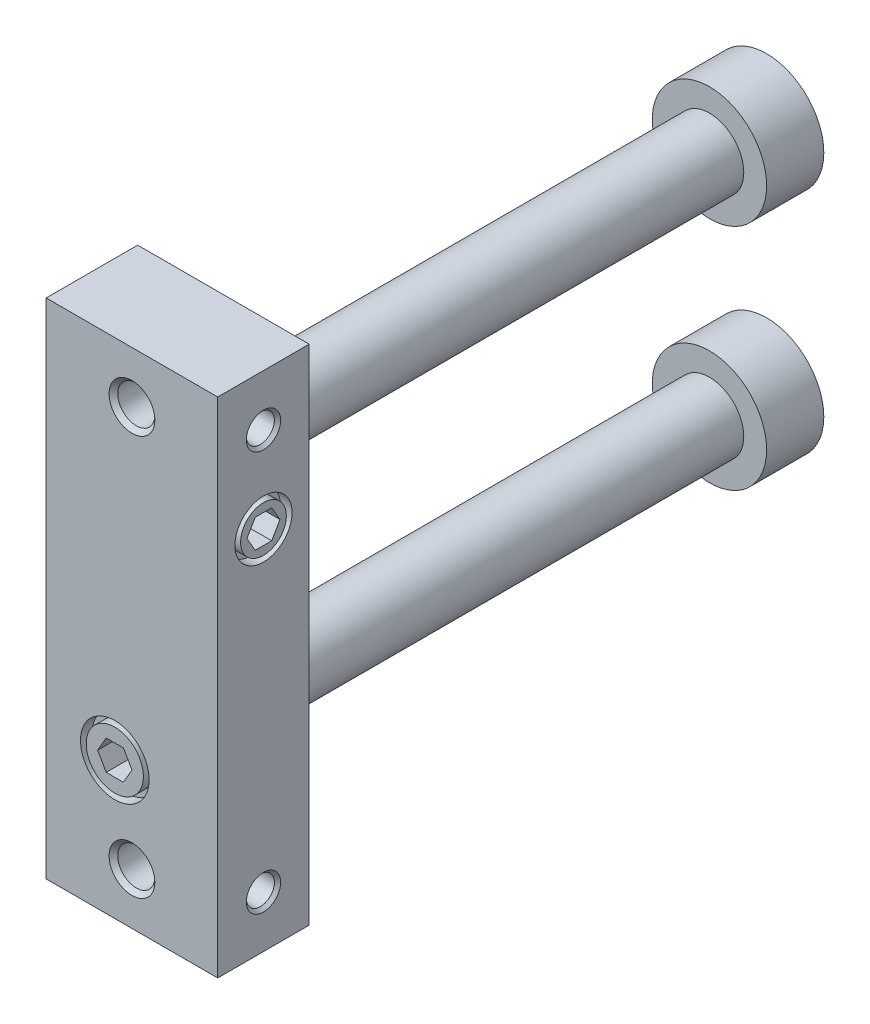
SolidWorks part; units mm, degrees
ref_plane "前视基准面" through (0, 0, 0) normal (0, 0, 1) x (1, 0, 0)
ref_plane "上视基准面" through (0, 0, 0) normal (0, 1, 0) x (1, 0, 0)
ref_plane "右视基准面" through (0, 0, 0) normal (1, 0, 0) x (0, 0, -1)
ref_plane "基准面1" through (0, 0, 9) normal (0, 0, 1) x (1, 0, 0)
sketch "草图1" plane through (0, 0, 9) normal (0, 0, 1) x (1, 0, 0)
  line L0 (-6, 22) -> (-6, -22)
  line L1 (-6, -22) -> (9, -22)
  line L2 (9, -22) -> (9, 22)
  line L3 (9, 22) -> (-6, 22)
extrude "凸台-拉伸1" add sketch "草图1" along normal blind 8
sketch "草图2" plane through (0, 0, 0) normal (1, 0, 0) x (0, 0, -1)
  line L0 (-14, 10) -> (-14, 13)
  line L1 (-14, 13) -> (35, 13)
  line L2 (35, 13) -> (35, 15)
  line L3 (35, 15) -> (40, 15)
  line L4 (40, 15) -> (40, 10)
  line L5 (40, 10) -> (-14, 10)
  line L6 (40, 10) -> (-14, 10) construction
revolve "旋转1" add sketch "草图2" angle 360 about L6 reverse direction yes
sketch "草图3" plane through (0, 0, 0) normal (1, 0, 0) x (0, 0, -1)
  line L0 (-14, -10) -> (-14, -7)
  line L1 (-14, -7) -> (35, -7)
  line L2 (35, -7) -> (35, -5)
  line L3 (35, -5) -> (40, -5)
  line L4 (40, -5) -> (40, -10)
  line L5 (40, -10) -> (-14, -10)
  line L6 (40, -10) -> (-14, -10) construction
revolve "旋转2" add sketch "草图3" angle 360 about L6 reverse direction yes
ref_plane "基准面2" through (1.5, 0, 0) normal (1, 0, 0) x (0, 0, -1)
sketch "草图4" plane through (1.5, 0, 0) normal (1, 0, 0) x (0, 0, -1)
  line L0 (-17, 17.5) -> (-17, 19.5)
  line L1 (-17, 19.5) -> (-16.621, 19.121)
  line L2 (-16.621, 19.121) -> (-9.379, 19.121)
  line L3 (-9.379, 19.121) -> (-9, 19.5)
  line L4 (-9, 19.5) -> (-9, 17.5)
  line L5 (-9, 17.5) -> (-17, 17.5)
  line L6 (-9, 17.5) -> (-17, 17.5) construction
revolve "切除-旋转1" cut sketch "草图4" angle 360 about L6 reverse direction yes
cosmetic thread "装饰螺纹线1" parameters "D1"=8, "D2"=4
sketch "草图5" plane through (1.5, 0, 0) normal (1, 0, 0) x (0, 0, -1)
  line L0 (-17, -17.5) -> (-17, -15.5)
  line L1 (-17, -15.5) -> (-16.621, -15.879)
  line L2 (-16.621, -15.879) -> (-9.379, -15.879)
  line L3 (-9.379, -15.879) -> (-9, -15.5)
  line L4 (-9, -15.5) -> (-9, -17.5)
  line L5 (-9, -17.5) -> (-17, -17.5)
  line L6 (-9, -17.5) -> (-17, -17.5) construction
revolve "切除-旋转2" cut sketch "草图5" angle 360 about L6 reverse direction yes
cosmetic thread "装饰螺纹线2" parameters "D1"=8, "D2"=4
ref_plane "基准面3" through (0, 0, 13) normal (0, 0, 1) x (1, 0, 0)
sketch "草图6" plane through (0, 0, 13) normal (0, 0, 1) x (1, 0, 0)
  line L0 (-6, 17.5) -> (-6, 19)
  line L1 (-6, 19) -> (-5.7295, 18.7295)
  line L2 (-5.7295, 18.7295) -> (-1, 18.7295)
  line L3 (-1, 18.7295) -> (-0.2901, 17.5)
  line L4 (-0.2901, 17.5) -> (-6, 17.5)
  line L5 (-0.2901, 17.5) -> (-6, 17.5) construction
revolve "切除-旋转3" cut sketch "草图6" angle 360 about L5 reverse direction yes
cosmetic thread "装饰螺纹线3" parameters "D1"=5, "D2"=3
sketch "草图7" plane through (0, 0, 13) normal (0, 0, 1) x (1, 0, 0)
  line L0 (-0.2901, -17.5) -> (-1, -18.7295)
  line L1 (-1, -18.7295) -> (-5.7295, -18.7295)
  line L2 (-5.7295, -18.7295) -> (-6, -19)
  line L3 (-6, -19) -> (-6, -17.5)
  line L4 (-6, -17.5) -> (-0.2901, -17.5)
  line L5 (-6, -17.5) -> (-0.2901, -17.5) construction
revolve "切除-旋转4" cut sketch "草图7" angle 360 about L5 reverse direction yes
cosmetic thread "装饰螺纹线4" parameters "D1"=5, "D2"=3
sketch "草图8" plane through (0, 0, 13) normal (0, 0, 1) x (1, 0, 0)
  line L0 (3.2901, 17.5) -> (4, 18.7295)
  line L1 (4, 18.7295) -> (8.7295, 18.7295)
  line L2 (8.7295, 18.7295) -> (9, 19)
  line L3 (9, 19) -> (9, 17.5)
  line L4 (9, 17.5) -> (3.2901, 17.5)
  line L5 (9, 17.5) -> (3.2901, 17.5) construction
revolve "切除-旋转5" cut sketch "草图8" angle 360 about L5 reverse direction yes
cosmetic thread "装饰螺纹线5" parameters "D1"=5, "D2"=3
sketch "草图9" plane through (0, 0, 13) normal (0, 0, 1) x (1, 0, 0)
  line L0 (9, -17.5) -> (9, -19)
  line L1 (9, -19) -> (8.7295, -18.7295)
  line L2 (8.7295, -18.7295) -> (4, -18.7295)
  line L3 (4, -18.7295) -> (3.2901, -17.5)
  line L4 (3.2901, -17.5) -> (9, -17.5)
  line L5 (3.2901, -17.5) -> (9, -17.5) construction
revolve "切除-旋转6" cut sketch "草图9" angle 360 about L5 reverse direction yes
cosmetic thread "装饰螺纹线6" parameters "D1"=5, "D2"=3
ref_plane "基准面4" through (0, 0, 17) normal (0, 0, 1) x (1, 0, 0)
sketch "草图10" plane through (0, 0, 17) normal (0, 0, 1) x (1, 0, 0)
  circle A0 centre (0, -10) radius 3
  circle A1 centre (0, -10) radius 2.5
extrude "切除-拉伸1" cut sketch "草图10" against normal blind 1
sketch "草图11" plane through (0, 0, 17) normal (0, 0, 1) x (1, 0, 0)
  line L0 (-1.5011, -10) -> (-0.7506, -11.3)
  line L1 (-0.7506, -11.3) -> (0.7506, -11.3)
  line L2 (0.7506, -11.3) -> (1.5011, -10)
  line L3 (1.5011, -10) -> (0.7506, -8.7)
  line L4 (0.7506, -8.7) -> (-0.7506, -8.7)
  line L5 (-0.7506, -8.7) -> (-1.5011, -10)
extrude "切除-拉伸2" cut sketch "草图11" against normal blind 2.6
ref_plane "基准面5" through (9, 0, 0) normal (1, 0, 0) x (0, 0, -1)
sketch "草图12" plane through (9, 0, 0) normal (1, 0, 0) x (0, 0, -1)
  circle A0 centre (-13, 10) radius 2.5
  circle A1 centre (-13, 10) radius 2
extrude "切除-拉伸3" cut sketch "草图12" against normal blind 1
sketch "草图13" plane through (9, 0, 0) normal (1, 0, 0) x (0, 0, -1)
  line L0 (-14.4434, 10) -> (-13.7217, 8.75)
  line L1 (-13.7217, 8.75) -> (-12.2783, 8.75)
  line L2 (-12.2783, 8.75) -> (-11.5566, 10)
  line L3 (-11.5566, 10) -> (-12.2783, 11.25)
  line L4 (-12.2783, 11.25) -> (-13.7217, 11.25)
  line L5 (-13.7217, 11.25) -> (-14.4434, 10)
extrude "切除-拉伸4" cut sketch "草图13" against normal blind 2.5
ref_plane "rod_body XY" through (0, 0, 0) normal (0, 0, -1) x (-1, 0, 0)
ref_plane "rod_body XZ" through (0, 0, 0) normal (0, 1, 0) x (1, 0, 0)
ref_plane "rod_body YZ" through (0, 0, 0) normal (1, 0, 0) x (0, 0, -1)
ref_axis "rod_body X" through (-80.9, 0, 0) along (1, 0, 0)
ref_axis "rod_body Y" through (0, 50, 0) along (0, -1, 0)
ref_axis "rod_body Z" through (0, 0, -80.9) along (0, 0, 1)
sketch3d "rod_body"
  point P0 (0, 0, 0)
